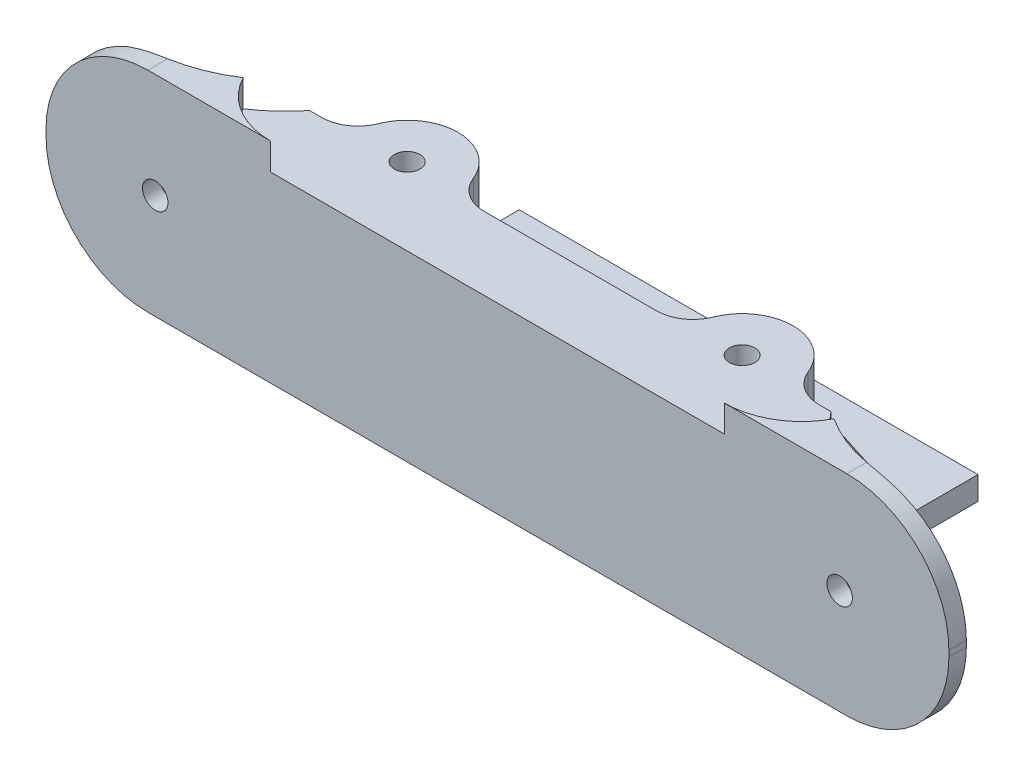
SolidWorks part; units mm, degrees
material "6061 Alloy"
ref_plane "Front Plane" through (0, 0, 0) normal (0, 0, 1) x (1, 0, 0)
ref_plane "Top Plane" through (0, 0, 0) normal (0, 1, 0) x (1, 0, 0)
ref_plane "Right Plane" through (0, 0, 0) normal (1, 0, 0) x (0, 0, -1)
sketch "Sketch5" plane through (0, 0, 0) normal (0, 1, 0) x (1, 0, 0)
  line L0 (-62, 0) -> (62, 0)
  line L1 (-62, 0) -> (-62, 2.4)
  line L2 (-31.5, 34.5) -> (31.5, 34.5)
  line L3 (62, 0) -> (62, 2.4)
  line L4 (-62, 2.4) -> (-51.5, 2.4)
  line L5 (-31.5, 34.5) -> (-31.5, 22.4)
  line L6 (31.5, 34.5) -> (31.5, 22.4)
  line L7 (62, 2.4) -> (51.5, 2.4)
  arc A0 (-51.5, 2.4) -> (-31.5, 22.4) centre (-51.5, 22.4) ccw
  arc A1 (51.5, 2.4) -> (31.5, 22.4) centre (51.5, 22.4) cw
  dimension "D5" = 40
  dimension "D7" = 20
  dimension "D1" = 124
  dimension "D2" = 63
  dimension "D3" = 34.5
  dimension "D4" = 2.4
  dimension "D6" = 10.5
  dimension "D8" = 12.1
  dimension "D9" = 10.5
  dimension "D10" = 12.1
  dimension "D11" = 2.4
extrude "Boss-Extrude1" add sketch "Sketch5" against normal blind 3.2
sketch "Sketch8" plane through (0, 0, 0) normal (0, 1, 0) x (1, 0, 0)
  line L0 (-35.808, 10) -> (35.808, 10)
  line L1 (-62, 0) -> (62, 0) construction
  line L2 (62, 2.4) -> (51.5, 2.4) construction
  line L3 (-62, 2.4) -> (-62, 0) construction
  line L4 (-51.5, 2.4) -> (-62, 2.4) construction
  line L5 (62, 2.4) -> (51.5, 2.4)
  line L6 (-62, 0) -> (62, 0)
  line L7 (-62, 2.4) -> (-62, 0)
  line L8 (-51.5, 2.4) -> (-62, 2.4)
  line L9 (62, 0) -> (62, 2.4) construction
  line L10 (62, 0) -> (62, 2.4)
  arc A0 (-51.5, 2.4) -> (-31.5, 22.4) centre (-51.5, 22.4) ccw construction
  arc A1 (31.5, 22.4) -> (51.5, 2.4) centre (51.5, 22.4) ccw construction
  arc A2 (35.808, 10) -> (51.5, 2.4) centre (51.5, 22.4) ccw
  arc A3 (-51.5, 2.4) -> (-35.808, 10) centre (-51.5, 22.4) ccw
  dimension "D1" = 10
extrude "Boss-Extrude2" add sketch "Sketch8" along normal blind 25.6 contours L10 L5 A2 L0 A3 L8 L7 L6
sketch "Sketch9" plane through (0, 0, 0) normal (0, 1, 0) x (1, 0, 0)
  line L0 (-62, 0) -> (62, 0) construction
  circle A0 centre (-23, 10.6) radius 7
  circle A1 centre (23, 10.6) radius 7
  dimension "D1" = 14
  dimension "D2" = 14
  dimension "D3" = 10.6
  dimension "D4" = 46
  dimension "D5" = 23
extrude "Boss-Extrude3" add sketch "Sketch9" along normal blind 25.6 contours A0 | A1
ref_plane "Plane1" through (23, 0, 0) normal (1, 0, 0) x (0, 0, -1)
sketch "Sketch10" plane through (23, 0, 0) normal (1, 0, 0) x (0, 0, -1)
  line L0 (16.2, 16.6) -> (16.2, 0)
  line L1 (22.4, 0) -> (10, 0) construction
  line L2 (17.6, 25.6) -> (10, 25.6) construction
  line L3 (16.2, 16.6) -> (27.5, 0)
  line L4 (22.4, 0) -> (34.5, 0) construction
  line L5 (34.5, -3.2) -> (34.5, 0) construction
  line L6 (16.2, 0) -> (27.5, 0)
  dimension "D1" = 9
  dimension "D2" = 7
  dimension "D3" = 11.3
extrude "Boss-Extrude4" add sketch "Sketch10" along normal mid plane 4 contours L6 L3 L0
ref_plane "Plane2" through (-23, 0, 0) normal (1, 0, 0) x (0, 0, -1)
extrude "Boss-Extrude5" add sketch "Sketch10<4>" along normal mid plane 4 from surface starting at plane "Plane2"
sketch "Sketch10<4>" plane through (23, 0, 0) normal (1, 0, 0) x (0, 0, -1) same geometry as "Sketch10"
fillet "Fillet2" radius 14 4 edges at (62, -3.2, -1.2) (62, 25.6, -1.2) (-62, -3.2, -1.2) (-62, 25.6, -1.2)
sketch "Sketch12" plane through (0, 0, 0) normal (0, 0, 1) x (1, 0, 0)
  line L0 (-48, 25.6) -> (-48, -3.2) construction
  circle A0 centre (-47, 11.2) radius 1.75
  circle A1 centre (47, 11.2) radius 1.75
  point P6 (-48, 11.2)
  dimension "D1" = 3.5
  dimension "D2" = 3.5
  dimension "D3" = 94
  dimension "D4" = 47
extrude "Cut-Extrude1" cut sketch "Sketch12" against normal through all contours A1 | A0
sketch "Sketch15" plane through (0, 0, -2.4) normal (0, 0, -1) x (-1, 0, 0)
  circle A0 centre (-47, 11.2) radius 3.5
  circle A1 centre (-47, 11.2) radius 1.75 construction
  circle A2 centre (47, 11.2) radius 3.5
  dimension "D1" = 7
extrude "Cut-Extrude4" cut sketch "Sketch15" along normal through all
sketch "Sketch16" plane through (0, 25.6, 0) normal (0, 1, 0) x (1, 0, 0)
  circle A0 centre (-23, 10.6) radius 1.75
  arc A1 (-16.0258, 10) -> (-21, 17.3082) centre (-23, 10.6) ccw construction
  circle A2 centre (23, 10.6) radius 1.75
  arc A3 (29.9742, 10) -> (25, 17.3082) centre (23, 10.6) ccw construction
  dimension "D1" = 3.5
  dimension "D2" = 3.5
extrude "Cut-Extrude5" cut sketch "Sketch16" against normal through all contours A0 | A2
sketch "Sketch17" plane through (0, 25.6, 0) normal (0, 1, 0) x (1, 0, 0)
  line L0 (-31.2, 10.6) -> (31.2, 10.6) construction
  line L1 (-31.2, 21.2) -> (31.2, 21.2)
  line L2 (-31.2, 0) -> (31.2, 0)
  line L5 (-48, 0) -> (48, 0) construction
  arc A0 (-31.2, 21.2) -> (-31.2, 0) centre (-31.2, 10.6) ccw
  arc A1 (31.2, 0) -> (31.2, 21.2) centre (31.2, 10.6) ccw
  circle A2 centre (-23, 10.6) radius 1.75 construction
  circle A3 centre (-23, 10.6) radius 1.75
  point P2 (0, 10.6)
  dimension "D1" = 62.4
extrude "Cut-Extrude6" cut sketch "Sketch17" against normal blind 3.7 contours L2 A1 L1 A0
fillet "Fillet3" radius 5 4 edges at (29.9742, 10.95, -10) (16.0258, 10.95, -10) (-16.0258, 10.95, -10) (-29.9742, 10.95, -10)
